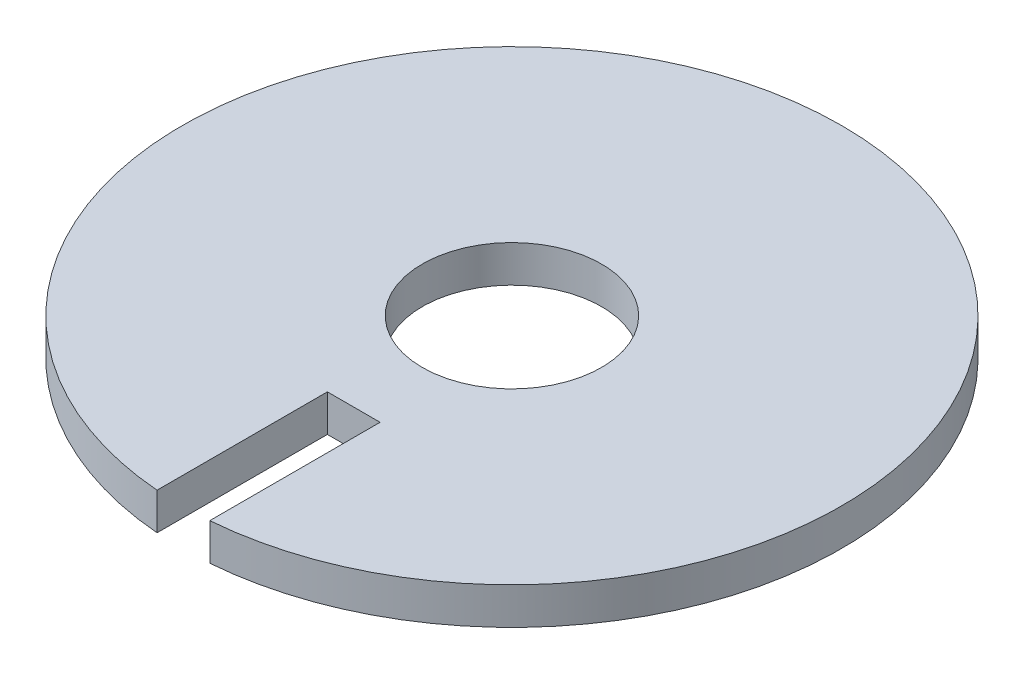
SolidWorks part; units mm, degrees
material "Plain Carbon Steel"
ref_plane "Front Plane" through (0, 0, 0) normal (0, 0, 1) x (1, 0, 0)
ref_plane "Top Plane" through (0, 0, 0) normal (0, 1, 0) x (1, 0, 0)
ref_plane "Right Plane" through (0, 0, 0) normal (1, 0, 0) x (0, 0, -1)
sketch "Sketch1" plane through (0, 0, 0) normal (0, 1, 0) x (1, 0, 0)
  circle A0 centre (0, 0) radius 6.25
  dimension "D1" = 12.5
sheet metal parameters "Sheet-Metal1" thickness 0.7 parameters "D1"=0.7366
base flange "Base-Flange1" sketch "Sketch1" thickness 0.7 reverse thickness direction no parameters "D1"=0.7366
sketch "Sketch4" plane through (0, 0, 0) normal (0, 1, 0) x (1, 0, 0)
  line L1 (-0.5, -3) -> (0.5, -3)
  line L2 (-0.5, -3) -> (-0.5, -6.25)
  line L3 (-0.5, -6.25) -> (0.5, -6.25)
  line L4 (0.5, -3) -> (0.5, -6.25)
  circle A0 centre (0, 0) radius 6.25 construction
  point P4 (0, -3)
  dimension "D1" = 3
  dimension "D2" = 1
extrude "Cut-Extrude1" cut sketch "Sketch4" against normal blind 0.7 normal cut yes
sketch "Sketch5" plane through (0, 0, 0) normal (0, 1, 0) x (1, 0, 0)
  circle A0 centre (0, 0) radius 1.7
  arc A1 (0.5, -6.23) -> (-0.5, -6.23) centre (0, 0) ccw construction
  dimension "D1" = 3.4
extrude "Cut-Extrude2" cut sketch "Sketch5" against normal blind 0.7 normal cut yes
flat pattern "Flat-Pattern1" [suppressed]
sketch "Bend-Lines1" plane through (0, 0, 0) normal (0, 1, 0) x (1, 0, 0)
sketch3d "Bounding-Box1" [suppressed]
  line L0 (-6.2652, -6.2347, 0) -> (6.2346, -6.2652, 0) construction
  line L1 (-6.2346, 6.265, 0) -> (6.2652, 6.2345, 0) construction
  line L2 (-6.2652, -6.2347, 0) -> (-6.2346, 6.265, 0) construction
  line L3 (6.2346, -6.2652, 0) -> (6.2652, 6.2345, 0) construction
